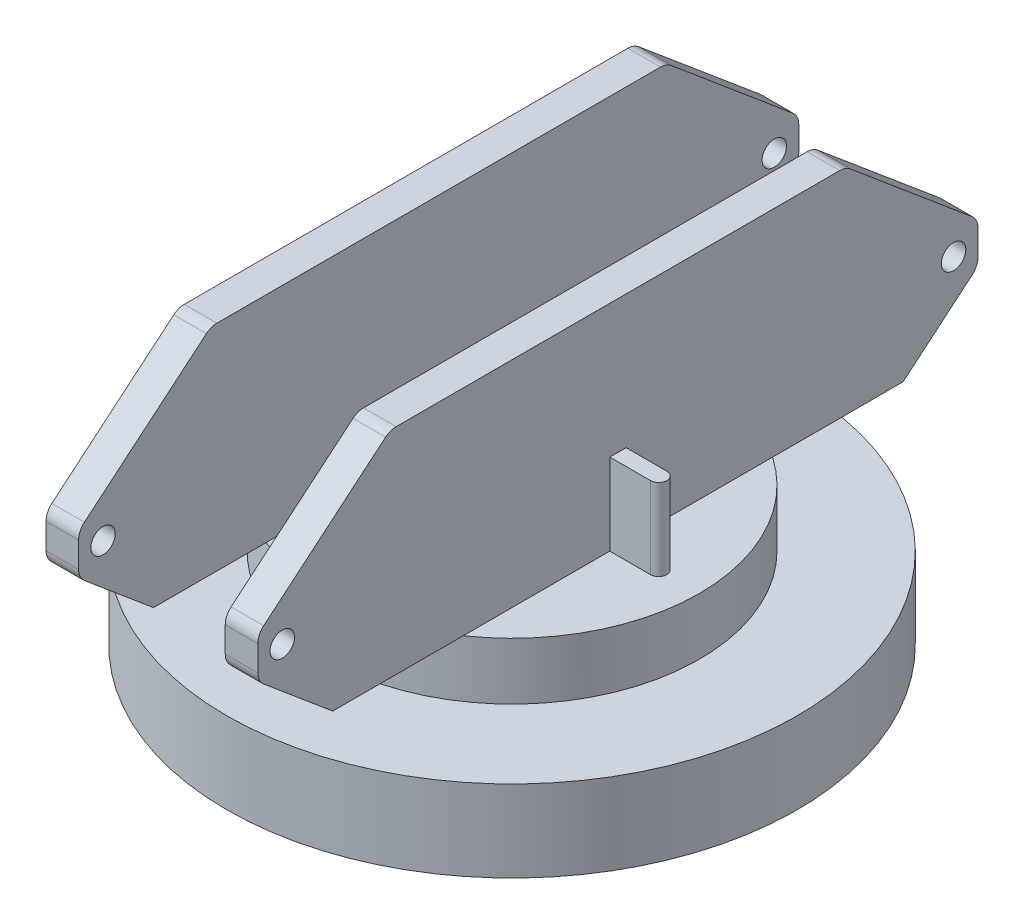
SolidWorks part; units mm, degrees
ref_plane "Front Plane" through (0, 0, 0) normal (0, 0, 1) x (1, 0, 0)
ref_plane "Top Plane" through (0, 0, 0) normal (0, 1, 0) x (1, 0, 0)
ref_plane "Right Plane" through (0, 0, 0) normal (1, 0, 0) x (0, 0, -1)
sketch "Sketch1" plane through (0, 0, 0) normal (0, 1, 0) x (1, 0, 0)
  circle A0 centre (0, 0) radius 35
  dimension "D1" = 70
extrude "Boss-Extrude1" add sketch "Sketch1" along normal blind 10
sketch "Sketch2" plane through (0, 10, 0) normal (0, 1, 0) x (1, 0, 0)
  circle A0 centre (0, 0) radius 23
  dimension "D1" = 46
extrude "Boss-Extrude2" add sketch "Sketch2" along normal blind 7
ref_plane "Plane1" through (13, 0, 0) normal (1, 0, 0) x (0, 0, -1)
sketch "Sketch4" plane through (13, 0, 0) normal (1, 0, 0) x (0, 0, -1)
  line L0 (0, 17) -> (0, 43.3433) construction
  line L1 (23, 17) -> (-23, 17) construction
  line L2 (0, 17) -> (-40.8827, 17) construction
  line L3 (-27.952, 17) -> (-27.952, 43.3433) construction
  line L4 (35, 17) -> (-35, 17)
  line L5 (-35, 17) -> (-44.194, 24.7147)
  line L6 (-44.194, 24.7147) -> (-44.194, 29.7147)
  line L7 (-44.194, 29.7147) -> (-27.952, 43.3433)
  line L8 (-27.952, 43.3433) -> (27.952, 43.3433)
  line L9 (-44.194, 20.0215) -> (-44.194, 37.4483) construction
  line L10 (35, 17) -> (44.194, 24.7147)
  line L11 (44.194, 24.7147) -> (44.194, 29.7147)
  line L12 (44.194, 29.7147) -> (27.952, 43.3433)
  dimension "D1" = 35
  dimension "D2" = 40
  dimension "D3" = 50
  dimension "D4" = 5
  dimension "D5" = 27.952
  dimension "D6" = 44.194
extrude "Boss-Extrude3" add sketch "Sketch4" against normal blind 4
sketch "Sketch5" plane through (13, 0, 0) normal (1, 0, 0) x (0, 0, -1)
  line L0 (0, 10) -> (0, 43.3433) construction
  line L1 (35, 10) -> (-35, 10) construction
  line L2 (27.952, 43.3433) -> (-27.952, 43.3433) construction
  line L3 (-44.194, 29.7147) -> (-44.194, 24.7147) construction
  circle A0 centre (-41.194, 27.2147) radius 1.5
  circle A1 centre (41.194, 27.2147) radius 1.5
  point P10 (-44.194, 27.2147)
  dimension "D1" = 3
  dimension "D2" = 3
extrude "Cut-Extrude1" cut sketch "Sketch5" against normal blind 4
fillet "Fillet1" radius 2 6 edges at (11, 43.3433, 27.952) (11, 43.3433, -27.952) (11, 29.7147, -44.194) (11, 24.7147, -44.194) (11, 24.7147, 44.194) (11, 29.7147, 44.194)
mirror "Mirror1" about plane through (0, 0, 0) normal (1, 0, 0) of "Fillet1", "Cut-Extrude1", "Boss-Extrude3"
sketch "Sketch6" plane through (0, 17, 0) normal (0, 1, 0) x (1, 0, 0)
  line L0 (-13, 0) -> (-19, 0) construction
  line L1 (-13, -18.9737) -> (-13, 18.9737) construction
  line L2 (-19, -1) -> (-13, -1)
  line L3 (-13, -1) -> (-13, 1)
  line L4 (-19, -1) -> (-19, 1)
  line L5 (-19, 1) -> (-13, 1)
  dimension "D1" = 6
  dimension "D2" = 1
extrude "Boss-Extrude4" add sketch "Sketch6" along normal blind 10
fillet "Fillet2" 2 edges at (-19, 22, 1) (-19, 22, -1) type full round first side face at (-16, 22, 1) second side face at (-16, 22, -1) middle face at (-19, 22, 0)
mirror "Mirror2" about plane through (0, 0, 0) normal (1, 0, 0) of "Fillet2", "Boss-Extrude4"
sketch "Sketch7" plane through (0, 0, 0) normal (0, -1, 0) x (1, 0, 0)
  circle A0 centre (0, 0) radius 15
  dimension "D1" = 30
extrude "Cut-Extrude2" cut sketch "Sketch7" against normal blind 10
